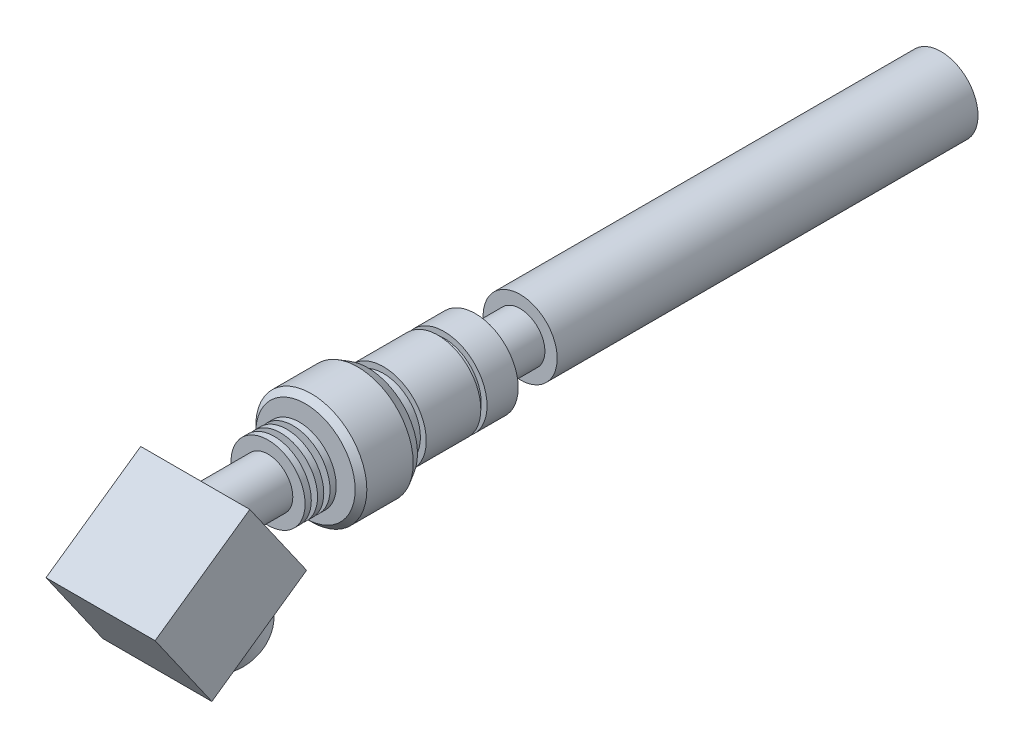
SolidWorks part; units mm, degrees
other "Детальный элемент1"
ref_plane "Спереди" through (0, 0, 0) normal (0, 0, 1) x (1, 0, 0)
ref_plane "Сверху" through (0, 0, 0) normal (0, 1, 0) x (1, 0, 0)
ref_plane "Справа" through (0, 0, 0) normal (1, 0, 0) x (0, 0, -1)
sketch "Эскиз1" plane through (0, 0, 0) normal (0, 0, 1) x (1, 0, 0)
  circle A0 centre (0, 0) radius 9.5
  dimension "D1" = 19
extrude "Бобышка-Вытянуть1" add sketch "Эскиз1" along normal blind 108
sketch "Эскиз2" plane through (0, 0, 108) normal (0, 0, 1) x (1, 0, 0)
  circle A0 centre (0, 0) radius 6.35
  dimension "D1" = 12.7
extrude "Бобышка-Вытянуть2" add sketch "Эскиз2" along normal blind 11.5
sketch "Эскиз3" plane through (0, 0, 119.5) normal (0, 0, 1) x (1, 0, 0)
  circle A0 centre (0, 0) radius 11
  dimension "D1" = 22
extrude "Бобышка-Вытянуть3" add sketch "Эскиз3" along normal blind 8
sketch "Эскиз4" plane through (0, 0, 127.5) normal (0, 0, 1) x (1, 0, 0)
  circle A0 centre (0, 0) radius 9.5
  dimension "D1" = 19
extrude "Бобышка-Вытянуть4" add sketch "Эскиз4" along normal blind 1.6
sketch "Эскиз5" plane through (0, 0, 129.1) normal (0, 0, 1) x (1, 0, 0)
  circle A0 centre (0, 0) radius 11
  dimension "D1" = 22
extrude "Бобышка-Вытянуть5" add sketch "Эскиз5" along normal blind 14
sketch "Эскиз6" plane through (0, 0, 143.1) normal (0, 0, 1) x (1, 0, 0)
  circle A0 centre (0, 0) radius 9.5
  dimension "D1" = 19
extrude "Бобышка-Вытянуть6" add sketch "Эскиз6" along normal blind 4
sketch "Эскиз7" plane through (0, 0, 147.1) normal (0, 0, 1) x (1, 0, 0)
  circle A0 centre (0, 0) radius 14.25
  dimension "D1" = 28.5
extrude "Бобышка-Вытянуть7" add sketch "Эскиз7" along normal blind 16
chamfer "Фаска1" distance 1.5 angle 45 1 edges at (14.25, 0, 163.1)
sketch "Эскиз8" plane through (0, 0, 0) normal (1, 0, 0) x (0, 0, -1)
  line L0 (-163.1, 6.35) -> (-164.7, 6.35)
  line L1 (-163.1, 12.75) -> (-163.1, -12.75) construction
  line L2 (-164.7, 6.35) -> (-164.7, 9.5)
  line L3 (-164.7, 9.5) -> (-166.3, 9.5)
  line L4 (-166.3, 9.5) -> (-166.3, 6.35)
  line L5 (-166.3, 6.35) -> (-167.9, 6.35)
  line L6 (-167.9, 6.35) -> (-167.9, 9.5)
  line L7 (-167.9, 9.5) -> (-169.5, 9.5)
  line L8 (-169.5, 9.5) -> (-169.5, 6.35)
  line L9 (-169.5, 6.35) -> (-171.1, 6.35)
  line L10 (-171.1, 6.35) -> (-171.1, 9.5)
  line L11 (-171.1, 9.5) -> (-172.7, 9.5)
  line L12 (-172.7, 9.5) -> (-172.7, 6.35)
  line L13 (-172.7, 6.35) -> (-193.1, 6.35)
  line L14 (-193.1, 6.35) -> (-193.1, 0)
  line L15 (-193.1, 0) -> (-163.1, 0)
  line L16 (-163.1, 0) -> (-163.1, 6.35)
  dimension "D1" = 1.6
  dimension "D2" = 1.6
  dimension "D3" = 9.5
  dimension "D4" = 6.35
  dimension "D5" = 30
revolve "Повернуть1" add sketch "Эскиз8" angle 360 about L15
sketch "Эскиз9" plane through (0, 0, 0) normal (1, 0, 0) x (0, 0, -1)
  line L0 (-179.6537, -6.35) -> (-188.5463, 6.35)
  line L1 (-193.1, -6.35) -> (-172.7, -6.35) construction
  line L2 (-172.7, 6.35) -> (-193.1, 6.35) construction
  line L3 (-188.5463, 6.35) -> (-193.1, 6.35)
  line L4 (-193.1, 6.35) -> (-193.1, -6.35) construction
  line L5 (-193.1, 6.35) -> (-193.1, -6.35)
  line L6 (-193.1, -6.35) -> (-179.6537, -6.35)
  line L7 (-163.1, 12.75) -> (-163.1, -12.75) construction
  line L9 (-172.7, 6.35) -> (-172.7, -6.35) construction
  point P6 (-184.1, 0)
  point P11 (-163.1, 0)
  dimension "D1" = 21
  dimension "D2" = 35
extrude "Вырез-Вытянуть1" cut sketch "Эскиз9" against normal through all and the other way through all
sketch "Эскиз10" plane through (0, 0, 0) normal (1, 0, 0) x (0, 0, -1)
  line L0 (-176.8156, -10.4032) -> (-191.3844, 10.4032)
  line L1 (-191.3844, 10.4032) -> (-215.6881, -6.6144)
  line L2 (-215.6881, -6.6144) -> (-201.1193, -27.4209)
  line L3 (-201.1193, -27.4209) -> (-176.8156, -10.4032)
  line L4 (-188.5463, 6.35) -> (-179.6537, -6.35) construction
  point P6 (-184.1, 0)
  dimension "D1" = 25.4
  dimension "D2" = 29.6694
extrude "Бобышка-Вытянуть8" add sketch "Эскиз10" along normal blind 14 and the other way blind 14
sketch "Эскиз12" plane through (0, 76.0955, 53.2826) normal (0, -0.8192, -0.5736) x (1, 0, 0)
  line L0 (14, 165.6406) -> (-14, 165.6406) construction
  line L1 (14, 180.4752) -> (14, 150.8059) construction
  line L2 (-14, 180.4752) -> (-14, 150.8059) construction
  line L3 (0, 150.8059) -> (0, 180.4752) construction
  line L4 (-14, 150.8059) -> (14, 150.8059) construction
  line L5 (-14, 180.4752) -> (14, 180.4752) construction
  circle A0 centre (0, 165.6406) radius 8
  dimension "D1" = 16
extrude "Бобышка-Вытянуть9" add sketch "Эскиз12" along normal blind 3.2
sketch "Эскиз13" plane through (0, 73.4742, 51.4472) normal (0, -0.8192, -0.5736) x (1, 0, 0)
  circle A0 centre (0, 165.6406) radius 9.5
  dimension "D1" = 19
extrude "Бобышка-Вытянуть10" add sketch "Эскиз13" along normal blind 6.4
chamfer "Фаска2" distance 1.5 angle 60 1 edges at (14.25, 0, 147.1) first distance on face at (14.25, 0, 147.1)
